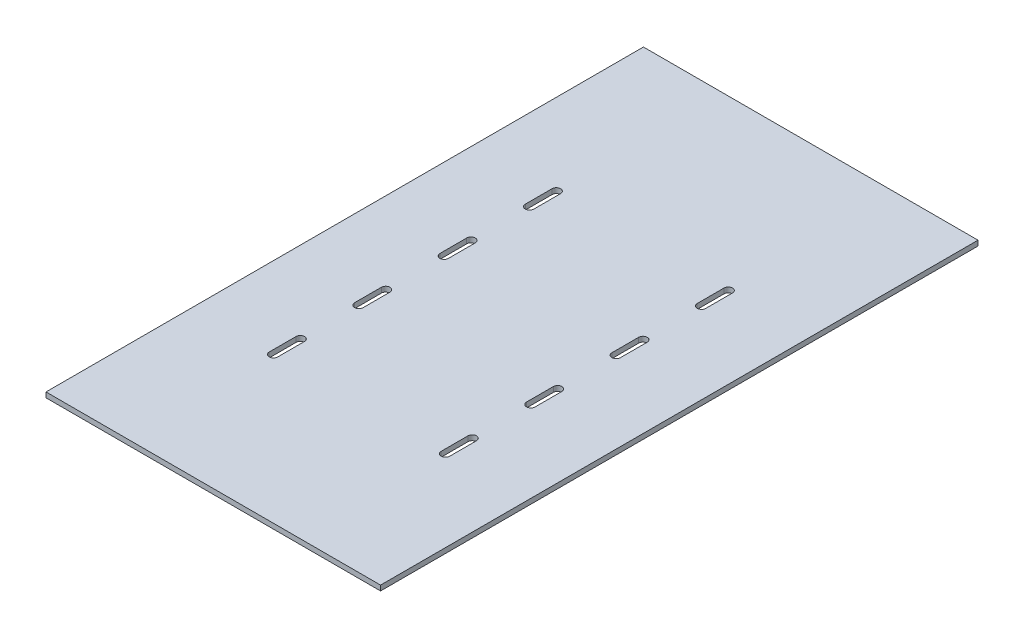
SolidWorks part; units mm, degrees
ref_plane "Front Plane" through (0, 0, 0) normal (0, 0, 1) x (1, 0, 0)
ref_plane "Top Plane" through (0, 0, 0) normal (0, 1, 0) x (1, 0, 0)
ref_plane "Right Plane" through (0, 0, 0) normal (1, 0, 0) x (0, 0, -1)
sketch "Sketch1" plane through (0, 0, 0) normal (0, 1, 0) x (1, 0, 0)
  line L1 (0, 0) -> (196, 0)
  line L2 (0, 0) -> (0, 350)
  line L3 (0, 350) -> (196, 350)
  line L4 (196, 0) -> (196, 350)
  dimension "D1" = 350
  dimension "D2" = 196
extrude "Boss-Extrude1" add sketch "Sketch1" along normal blind 3
hole_wizard "Ø5.0mm Dowel Slot1" positions "Sketch2" profile "Sketch3" size "Ø5.0" standard "ANSI Metric" slot yes end condition through all
sketch "Sketch2" plane through (0, 3, 0) normal (0, 1, 0) x (1, 0, 0)
  line L0 (47.625, 253.85) -> (47.625, 233.15) construction
  point P0 (47.625, 243.5)
  point P7 (148.375, 243.5)
  point P10 (148.375, 193.5)
  point P13 (47.625, 193.5)
  point P16 (47.625, 143.5)
  point P19 (148.375, 143.5)
  point P22 (47.625, 93.5)
  point P25 (148.375, 93.5)
  point P30 (0, 0)
  point P31 (0, 0)
  point P32 (0, 0)
  point P33 (0, 0)
  point P34 (0, 0)
  point P35 (0, 0)
  point P36 (0, 0)
  point P37 (0, 0)
  dimension "D1" = 20.7
sketch "Sketch3" plane through (47.625, 3, -243.5) normal (1, 0, 0) x (0, 0, 1)
  line L0 (0, 0) -> (0, 3)
  line L1 (0, 3) -> (2.5, 3)
  line L2 (2.5, 3) -> (2.5, 0)
  line L5 (2.5, 0) -> (0, 0)
  line L11 (0, -6.35) -> (0, 107.95) construction
  dimension "Thru Hole Dia." = 5
  dimension "Thru Hole Depth" = 3
